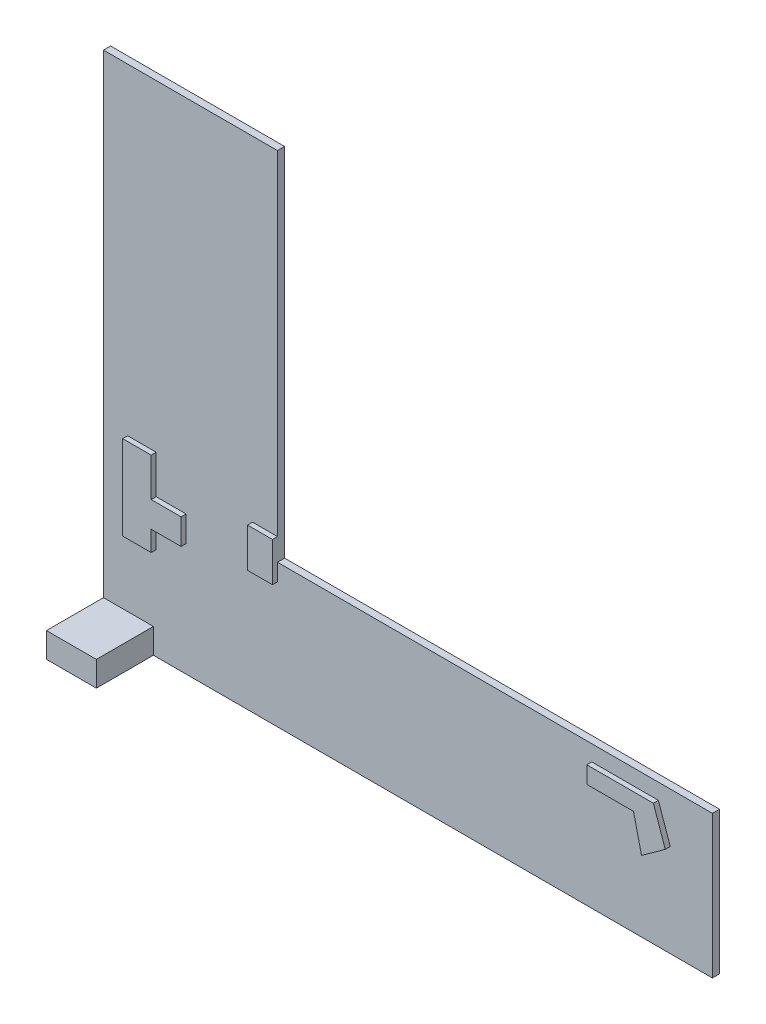
SolidWorks part; units mm, degrees
ref_plane "Front Plane" through (0, 0, 0) normal (0, 0, 1) x (1, 0, 0)
ref_plane "Top Plane" through (0, 0, 0) normal (0, 1, 0) x (1, 0, 0)
ref_plane "Right Plane" through (0, 0, 0) normal (1, 0, 0) x (0, 0, -1)
sketch "Sketch1" plane through (0, 0, 0) normal (0, 0, 1) x (1, 0, 0)
  line L1 (0, 0) -> (244, 0)
  line L2 (0, 0) -> (0, 700)
  line L3 (0, 700) -> (244, 700)
  line L4 (244, 0) -> (244, 700)
  line L5 (244, 200) -> (854, 200)
  line L6 (244, 200) -> (244, 0)
  line L7 (244, 0) -> (854, 0)
  line L8 (854, 200) -> (854, 0)
  dimension "D1" = 244
  dimension "D2" = 700
  dimension "D3" = 200
  dimension "D4" = 610
extrude "Boss-Extrude4" add sketch "Sketch1" along normal blind 10 contours L8 L5 L4 L7 | L1 L4 L3 L2 region at (122, 350, 0) region at (549, 100, 0)
sketch "Sketch3" plane through (0, 0, 10) normal (0, 0, 1) x (1, 0, 0)
  line L1 (0, 0) -> (70, 0)
  line L2 (0, 0) -> (0, 35)
  line L3 (0, 35) -> (70, 35)
  line L4 (70, 0) -> (70, 35)
  dimension "D1" = 70
  dimension "D2" = 35
extrude "Boss-Extrude6" add sketch "Sketch3" along normal blind 80
sketch "Sketch9" plane through (0, 0, 10) normal (0, 0, 1) x (1, 0, 0)
  line L0 (244, 200) -> (244, 700) construction
  line L1 (244, 231.1534) -> (209, 231.1534)
  line L2 (244, 231.1534) -> (244, 176.1534)
  line L3 (244, 176.1534) -> (209, 176.1534)
  line L4 (209, 231.1534) -> (209, 176.1534)
  dimension "D1" = 55
  dimension "D2" = 35
extrude "Boss-Extrude7" add sketch "Sketch9" along normal blind 7 contours L3 L4 L1 L2
sketch "Sketch11" plane through (0, 0, 10) normal (0, 0, 1) x (1, 0, 0)
  line L1 (33.8653, 248.5397) -> (73.8653, 248.5397)
  line L2 (33.8653, 248.5397) -> (33.8653, 130.1813)
  line L3 (33.8653, 130.1813) -> (73.8653, 130.1813)
  line L4 (73.8653, 248.5397) -> (73.8653, 130.1813)
  line L5 (73.8653, 158.539) -> (115.8191, 158.539)
  line L6 (73.8653, 158.539) -> (73.8653, 194.5317)
  line L7 (73.8653, 194.5317) -> (115.8191, 194.5317)
  line L8 (115.8191, 158.539) -> (115.8191, 194.5317)
  dimension "D1" = 40
extrude "Boss-Extrude9" add sketch "Sketch11" along normal blind 7 contours L5 L8 L7 L6 | L3 L4 L1 L2
sketch "Sketch12" plane through (0, 0, 10) normal (0, 0, 1) x (1, 0, 0)
  line L0 (750.3304, 154.096) -> (761.5998, 106.2559)
  line L1 (684.8107, 177.8893) -> (750.3304, 177.8893)
  line L2 (684.8107, 177.8893) -> (684.8107, 154.096)
  line L3 (684.8107, 154.096) -> (750.3304, 154.096)
  line L4 (750.3304, 177.8893) -> (750.3304, 154.096)
  line L5 (761.5998, 106.2559) -> (794.8628, 130.176)
  line L6 (794.8628, 130.176) -> (778.2313, 177.8893)
  line L7 (778.2313, 177.8893) -> (750.3304, 177.8893)
extrude "Boss-Extrude10" add sketch "Sketch12" along normal blind 7 contours L1 L7 L6 L5 L0 L3 L2
